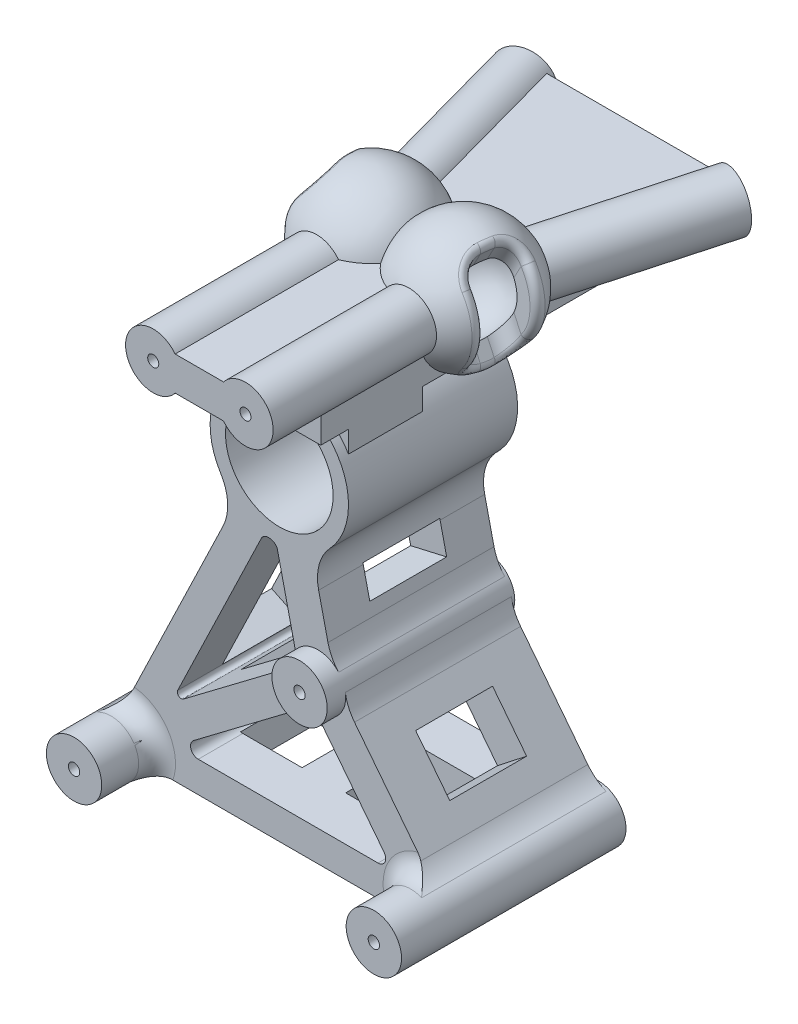
SolidWorks part; units mm, degrees
ref_plane "前视基准面" through (0, 0, 0) normal (0, 0, 1) x (1, 0, 0)
ref_plane "上视基准面" through (0, 0, 0) normal (0, 1, 0) x (1, 0, 0)
ref_plane "右视基准面" through (0, 0, 0) normal (1, 0, 0) x (0, 0, -1)
sketch "平面布局" plane through (0, 0, 0) normal (0, 1, 0) x (1, 0, 0)
  line L0 (-3, 0) -> (0, 0) construction
  line L1 (0, 0) -> (3, 0) construction
  line L2 (-3, -14.2) -> (-3, 0)
  line L3 (-3, 0) -> (-6.7739, 13.6893)
  line L4 (3, -14.2) -> (3, 0)
  line L5 (3, 0) -> (6.7739, 13.6893)
  line L6 (0, 0) -> (0, 13.6893) construction
  line L7 (0, 13.6893) -> (6.7739, 13.6893) construction
  line L8 (-6.7739, 13.6893) -> (0, 13.6893) construction
  line L9 (6.7739, 13.6893) -> (12.433, -1.2764) construction
  line L10 (12.433, -1.2764) -> (3, -14.2) construction
  line L11 (-6.7739, 13.6893) -> (-12.433, -1.2764) construction
  line L12 (-12.433, -1.2764) -> (-3, -14.2) construction
  line L13 (-12.433, -1.2764) -> (-3, 0) construction
  line L14 (3, 0) -> (12.433, -1.2764) construction
  dimension "D1" = 6
  dimension "D2" = 15.413
  dimension "D3" = 14.2
  dimension "D4" = 16
sketch "减速器布局" plane through (0, 0, 0) normal (0, 0, 1) x (1, 0, 0)
  line L0 (0, 0) -> (0, -27.1742) construction
  line L1 (0, -27.1742) -> (9.75, -27.1742) construction
  line L2 (0, -27.1742) -> (-9.75, -27.1742) construction
  line L3 (-3, 0) -> (0, 0) construction
  line L4 (-12.433, 0) -> (-3, 0) construction
  line L5 (0, 0) -> (3, 0) construction
  line L6 (12.433, 0) -> (3, 0) construction
  line L7 (3, 0) -> (12.433, 0) construction
  line L8 (9.75, -27.1742) -> (3, 0) construction
  line L9 (-3, 0) -> (-9.75, -27.1742) construction
  line L10 (9.75, -27.1742) -> (2.516, -17.9151) construction
  line L11 (-22.186, -2) -> (32.0919, -2) construction
  line L12 (0, 0) -> (0, -28.8801) construction
  line L13 (9.75, -27.1742) -> (16.95, -27.1742) construction
  line L14 (2.516, -17.9151) -> (0, -6.95) construction
  line L15 (0, -6.95) -> (0, 0) construction
  circle A0 centre (9.75, -27.1742) radius 11.75 construction
  circle A1 centre (-9.75, -27.1742) radius 11.75 construction
  circle A2 centre (2.516, -17.9151) radius 9.75 construction
  circle A3 centre (2.516, -17.9151) radius 2.5 construction
  circle A4 centre (-9.75, -27.1742) radius 1.8
  circle A5 centre (9.75, -27.1742) radius 1.8
  circle A6 centre (9.75, -27.1742) radius 10.25 construction
  circle A7 centre (-9.75, -27.1742) radius 10.25 construction
  circle A8 centre (2.516, -17.9151) radius 11.25 construction
  circle A9 centre (0, -28.8801) radius 3.5
  circle A10 centre (9.75, -27.1742) radius 9.125 construction
  circle A11 centre (-9.75, -27.1742) radius 9.125 construction
  circle A12 centre (9.75, -27.1742) radius 7.2 construction
  circle A13 centre (-9.75, -27.1742) radius 7.2 construction
  circle A14 centre (16.95, -27.1742) radius 1.6
  circle A15 centre (0, -6.95) radius 4.8
  dimension "D4" = 23.5
  dimension "D5" = 5
  dimension "D6" = 3.6
  dimension "D7" = 20.5
  dimension "D8" = 19.5
  dimension "D10" = 22.5
  dimension "D11" = 7
  dimension "D13" = 18.25
  dimension "D14" = 14.4
  dimension "D15" = 3.2
  dimension "D16" = 9.6
  dimension "D1" = 6
  dimension "D2" = 28
  dimension "D3" = 9.75
  dimension "D9" = 52
  dimension "D12" = 2
ref_plane "基准面1" through (3, 0, 14.2) normal (0, 0, -1) x (-1, 0, 0)
sketch "草图2" plane through (3, 0, 14.2) normal (0, 0, -1) x (-1, 0, 0)
  line L1 (4.5752, -1.1) -> (1.4248, -1.1)
  line L3 (4.5752, 1.1) -> (1.4248, 1.1)
  line L5 (4.5752, -1.1) -> (1.4248, 1.1) construction
  line L6 (4.5752, 1.1) -> (1.4248, -1.1) construction
  arc A0 (1.4248, 1.1) -> (1.4248, -1.1) centre (0, 0) ccw
  arc A1 (4.5752, -1.1) -> (4.5752, 1.1) centre (6, 0) ccw
  point P2 (3, 0)
  dimension "D1" = 3.6
  dimension "D2" = 2.2
extrude "凸台-拉伸1" add sketch "草图2" along normal up to vertex (14.2 mm away) up to point (-3, 0, 0)
ref_plane "基准面2" through (-6.7739, 0, -13.6893) normal (-0.2658, 0, -0.964) x (-0.964, 0, 0.2658)
sketch "草图3" plane through (-6.7739, 0, -13.6893) normal (-0.2658, 0, -0.964) x (-0.964, 0, 0.2658)
  line L0 (0, 0) -> (-2.8921, 0) construction
  line L1 (0, 0) -> (-6.5303, 0) construction
  circle A0 centre (0, 0) radius 1.8
  dimension "D1" = 3.6
extrude "凸台-拉伸2" add sketch "草图3" against normal blind 14
ref_plane "基准面3" through (6.7739, 0, -13.6893) normal (0.2658, 0, -0.964) x (-0.964, 0, -0.2658)
sketch "草图4" plane through (6.7739, 0, -13.6893) normal (0.2658, 0, -0.964) x (-0.964, 0, -0.2658)
  circle A0 centre (0, 0) radius 1.8
  dimension "D1" = 3.6
extrude "凸台-拉伸3" add sketch "草图4" against normal blind 14
sketch "草图10" plane through (0, 0, 0) normal (0, 1, 0) x (1, 0, 0)
  line L0 (-3, 0) -> (-6.7739, 13.6893) construction
  line L1 (-3, 0) -> (0, 0) construction
  line L2 (0, 0) -> (3, 0) construction
  line L3 (3, 0) -> (6.7739, 13.6893) construction
  line L4 (0, 13.6893) -> (6.7739, 13.6893) construction
  line L5 (-6.7739, 13.6893) -> (0, 13.6893) construction
  line L6 (-3, 0) -> (-6.7739, 13.6893)
  line L7 (-3, 0) -> (0, 0)
  line L8 (0, 0) -> (3, 0)
  line L9 (3, 0) -> (6.7739, 13.6893)
  line L10 (0, 13.6893) -> (6.7739, 13.6893)
  line L11 (-6.7739, 13.6893) -> (0, 13.6893)
extrude "凸台-拉伸4" add sketch "草图10" along normal mid plane 2.2
sketch "草图5" plane through (0, 0, 0) normal (0, 1, 0) x (1, 0, 0)
  line L0 (-7, 0) -> (-5.56, 0)
  line L1 (-0.44, 0) -> (0.44, 0)
  line L2 (5.56, 0) -> (7, 0)
  arc A0 (7, 0) -> (0, 2.6458) centre (3, 0) ccw
  arc A1 (0, 2.6458) -> (-7, 0) centre (-3, 0) ccw
  arc A2 (-5.56, 0) -> (-0.44, 0) centre (-3, 0) cw
  arc A3 (0.44, 0) -> (5.56, 0) centre (3, 0) cw
  dimension "D1" = 8
  dimension "D2" = 2.56
revolve "旋转1" add sketch "草图5" angle 360 about L0
sketch "草图8" plane through (0, 0, 0) normal (0, 1, 0) x (1, 0, 0)
  line L0 (-5.56, 0) -> (-0.44, 0)
  line L1 (0.44, 0) -> (5.56, 0)
  line L3 (-7, 0) -> (-5.56, 0)
  line L4 (-0.44, 0) -> (0.44, 0)
  line L5 (5.56, 0) -> (7, 0)
  line L7 (-0.44, 0) -> (0.44, 0)
  arc A4 (-0.44, 0) -> (-5.56, 0) centre (-3, 0) ccw
  arc A5 (5.56, 0) -> (0.44, 0) centre (3, 0) ccw
  arc A6 (7, 0) -> (0, 2.6458) centre (3, 0) ccw
  arc A7 (0, 2.6458) -> (-7, 0) centre (-3, 0) ccw
  arc A8 (-0.44, 0) -> (-5.56, 0) centre (-3, 0) ccw
  arc A9 (5.56, 0) -> (0.44, 0) centre (3, 0) ccw
  dimension "D1" = 0
revolve "切除-旋转2" cut sketch "草图8" angle 360 about L7 region at (-3, 0, -1.0865) region at (3, 0, -1.0865)
sketch "草图6" plane through (0, 0, 0) normal (0, 1, 0) x (1, 0, 0)
  line L0 (3, 0) -> (12.433, -1.2764) construction
  line L1 (3, 0) -> (12.433, -1.2764) construction
  line L2 (3, 0) -> (1.8263, -8.6738) construction
  line L3 (4.4608, -1.7113) -> (7.0032, -2.0554)
  line L4 (4.863, 1.2616) -> (7.4055, 0.9175)
  line L6 (3.2011, 1.4865) -> (12.6342, 0.21) construction
  line L7 (2.7989, -1.4865) -> (12.2319, -2.7629) construction
  arc A0 (4.4608, -1.7113) -> (4.863, 1.2616) centre (3, 0) ccw
  arc A1 (7.0032, -2.0554) -> (7.4055, 0.9175) centre (3, 0) ccw
  dimension "D1" = 4.5
  dimension "D2" = 9
  dimension "D3" = 1.5
  dimension "D4" = 1.5
revolve "切除-旋转1" cut sketch "草图6" angle 120 mid plane about L2
mirror "镜向1" about plane through (0, 0, 0) normal (1, 0, 0) of "切除-旋转1"
fillet "圆角1" radius 1.1 8 edges at (-4.6337, -2.5039, -1.2926) (-4.2315, -2.5039, 1.6803) (-4.2315, 2.5039, 1.6803) (-4.6337, 2.5039, -1.2926) (4.2315, -2.5039, 1.6803) (4.6337, -2.5039, -1.2926) (4.6337, 2.5039, -1.2926) (4.2315, 2.5039, 1.6803)
fillet "圆角2" radius 0.4 16 edges at (-6.8758, 0, -0.9892) (-5.2491, -3.2142, -0.7816) (-4.9819, -3.4641, 0.2682) (-5.0396, -3.0857, 1.5226) (-6.4735, 0, 1.9837) (-4.9605, 3.2142, 1.3512) (-4.9819, 3.4641, 0.2682) (-5.3709, 3.0857, -0.9258) (5.3709, -3.0857, -0.9258) (4.9819, -3.4641, 0.2682) (4.9605, -3.2142, 1.3512) (6.4735, 0, 1.9837) (5.0396, 3.0857, 1.5226) (4.9819, 3.4641, 0.2682) (5.2491, 3.2142, -0.7816) (6.8758, 0, -0.9892)
ref_plane "基准面4" through (0, -3.3, 0) normal (0, -1, 0) x (-1, 0, 0)
sketch "草图26" plane through (0, -3.3, 0) normal (0, -1, 0) x (-1, 0, 0)
  line L0 (0, 0) -> (0, -0.2) construction
  line L1 (-3.9, -10.2) -> (3.9, -10.2)
  line L2 (-3.9, -10.2) -> (-3.9, 9.8)
  line L3 (-3.9, 9.8) -> (3.9, 9.8)
  line L4 (3.9, -10.2) -> (3.9, 9.8)
  line L5 (-3.9, -10.2) -> (3.9, 9.8) construction
  line L6 (-3.9, 9.8) -> (3.9, -10.2) construction
  point P0 (0, -0.2)
  dimension "D1" = 7.8
  dimension "D2" = 20
  dimension "D3" = 0.2
extrude "凸台-拉伸9" add sketch "草图26" against normal up to body
sketch "草图12" plane through (0, 0, 0) normal (0, 0, 1) x (1, 0, 0)
  circle A0 centre (9.75, -27.1742) radius 1.8 construction
  circle A1 centre (9.75, -27.1742) radius 1.8
  circle A2 centre (-9.75, -27.1742) radius 1.8 construction
  circle A3 centre (-9.75, -27.1742) radius 1.8
  circle A4 centre (0, -6.95) radius 4.5
  circle A5 centre (2.516, -17.9151) radius 1.8
  circle A7 centre (0, -6.95) radius 3.5
  dimension "D1" = 7
  dimension "D2" = 9
extrude "凸台-拉伸5" add sketch "草图12" along normal blind 12.6 and the other way blind 2 separate body
sketch "草图13" plane through (0, 0, 12.6) normal (0, 0, 1) x (1, 0, 0)
  circle A1 centre (2.516, -17.9151) radius 1.8
  circle A2 centre (2.516, -17.9151) radius 1.8
  dimension "D1" = 0
extrude "切除-拉伸1" cut sketch "草图13" against normal blind 2.4
sketch "草图14" plane through (0, 0, 12.6) normal (0, 0, 1) x (1, 0, 0)
  circle A1 centre (0, -6.95) radius 4.5
  circle A2 centre (0, -6.95) radius 4.5
  dimension "D1" = 0
extrude "切除-拉伸2" cut sketch "草图14" against normal blind 3.6
sketch "草图15" plane through (0, 0, 0) normal (0, 0, 1) x (1, 0, 0)
  circle A0 centre (2.516, -17.9151) radius 0.37
  circle A1 centre (9.75, -27.1742) radius 0.37
  circle A2 centre (-9.75, -27.1742) radius 0.37
  dimension "D1" = 0.74
extrude "切除-拉伸3" cut sketch "草图15" against normal through all both and the other way through all
sketch "草图16" plane through (0, 0, 0) normal (0, 0, 1) x (1, 0, 0)
  line L0 (-9.75, -27.1742) -> (9.75, -27.1742) construction
  line L1 (9.75, -27.1742) -> (2.516, -17.9151) construction
  line L2 (2.516, -17.9151) -> (0, -6.95) construction
  line L3 (0, -6.95) -> (-9.75, -27.1742) construction
  line L4 (0, -6.95) -> (9.75, -27.1742) construction
  line L5 (-9.75, -27.1742) -> (2.516, -17.9151) construction
  line L6 (-2.8061, -10.4679) -> (-10.0008, -25.3918)
  line L7 (1.0463, -16.8758) -> (-0.1997, -11.4456)
  line L9 (-7.953, -27.0706) -> (1.9239, -19.6149)
  line L10 (-8.2533, -28.1742) -> (8.2533, -28.1742)
  line L11 (9.8696, -25.3782) -> (4.2876, -18.2335)
  line L12 (-9.75, -28.1742) -> (9.75, -28.1742) construction
  line L13 (-1.0045, -11.3365) -> (-8.1993, -26.2603)
  line L14 (-9.1579, -25.4744) -> (0.719, -18.0187)
  line L17 (-8.2533, -26.1742) -> (8.2533, -26.1742)
  line L21 (-0.9008, -6.5158) -> (-10.6508, -26.7399) construction
  line L22 (0.9008, -7.3843) -> (-8.8492, -27.6085) construction
  line L23 (10.6956, -26.4354) -> (3.4616, -17.1763) construction
  line L25 (7.9784, -26.8558) -> (2.3964, -19.7111)
  line L26 (-10.3525, -26.3761) -> (1.9135, -17.1169) construction
  line L27 (-9.75, -26.1742) -> (9.75, -26.1742) construction
  line L28 (-9.1475, -27.9723) -> (3.1185, -18.7132) construction
  line L30 (3.3855, -16.3391) -> (2.1396, -10.9089)
  circle A1 centre (0, -6.95) radius 4.5 construction
  circle A2 centre (2.516, -17.9151) radius 1.8 construction
  circle A3 centre (9.75, -27.1742) radius 1.8 construction
  circle A4 centre (-9.75, -27.1742) radius 1.8 construction
  circle A5 centre (0, -6.95) radius 4.5
  circle A6 centre (2.516, -17.9151) radius 1.8
  circle A7 centre (9.75, -27.1742) radius 1.8
  circle A8 centre (-9.75, -27.1742) radius 1.8
  point P3 (3.4906, -17.6914)
  point P5 (0.9747, -6.7264)
  point P12 (-0.9008, -7.3843)
  point P13 (8.8492, -27.6085)
  point P20 (8.962, -27.7899)
  point P21 (1.728, -18.5307)
  point P26 (1.5413, -18.1387)
  point P27 (-0.9747, -7.1737)
  point P28 (0.9008, -6.5158)
  point P29 (10.6508, -26.7399)
  dimension "D2" = 1.2
  dimension "D3" = 1.2
  dimension "D10" = 1.2
  dimension "D1" = 1
  dimension "D4" = 1
  dimension "D5" = 1
  dimension "D6" = 1.2
  dimension "D8" = 1
  dimension "D9" = 1
  dimension "D12" = 1
extrude "凸台-拉伸7" add sketch "草图16" along normal blind 9 and the other way blind 1.8 contours A6 L30 A5 L7 | A8 L14 L13 A5 L6 | A6 L14 L13 L17 L9 | A8 L10 A7 L25 L17 L9 | A7 L11 A6 L25 L17 | A7 L17 L25 | A8 L17 L13 L14 | A8 L9 L17 L13 region at (-5.3477, -17.9751, 0) region at (-8.1058, -25.1661, 0) region at (0.0882, -27.1948, 0) region at (1.5703, -13.7937, 0) region at (-3.1946, -22.2527, 0) region at (-7.6266, -26.4657, 0) region at (7.8774, -26.3936, 0) region at (6.1106, -22.4953, 0)
sketch "草图17" plane through (0, -1.1, 0) normal (0, -1, 0) x (1, 0, 0)
  line L0 (0, 0) -> (0, 6) construction
  line L2 (-3.9, 3.6) -> (3.9, 3.6)
  line L3 (-3.9, 3.6) -> (-3.9, 8.4)
  line L4 (-3.9, 8.4) -> (3.9, 8.4)
  line L5 (3.9, 3.6) -> (3.9, 8.4)
  line L6 (-3.9, 3.6) -> (3.9, 8.4) construction
  line L7 (-3.9, 8.4) -> (3.9, 3.6) construction
  dimension "D1" = 4.8
  dimension "D2" = 7.8
  dimension "D3" = 6
extrude "凸台-拉伸8" add sketch "草图17" along normal up to body
sketch "草图18" plane through (0, 0, 14.2) normal (0, 0, 1) x (1, 0, 0)
  line L0 (-12.433, 0) -> (-3, 0) construction
  line L1 (-12.433, 0) -> (-3, 0) construction
  line L2 (12.433, 0) -> (3, 0) construction
  line L3 (0, 0) -> (6.7739, 0) construction
  circle A0 centre (-3, 0) radius 0.36
  circle A1 centre (3, 0) radius 0.36
  arc A2 (3.9, -1.5588) -> (1.5752, 1.1) centre (3, 0) ccw construction
  arc A4 (-1.5752, 1.1) -> (-1.5752, -1.1) centre (-3, 0) ccw construction
  dimension "D1" = 0.72
extrude "切除-拉伸4" cut sketch "草图18" against normal blind 10
sketch "草图19" plane through (3.9858, 0, -14.458) normal (0.2658, 0, -0.964) x (-0.964, 0, -0.2658)
  circle A0 centre (-2.8921, 0) radius 0.36
  dimension "D1" = 0.72
extrude "切除-拉伸5" cut sketch "草图19" against normal blind 10
sketch "草图20" plane through (-3.9858, 0, -14.458) normal (-0.2658, 0, -0.964) x (-0.964, 0, 0.2658)
  circle A0 centre (2.8921, 0) radius 0.36
  dimension "D1" = 0.72
extrude "切除-拉伸6" cut sketch "草图20" against normal blind 10
sketch "草图21" plane through (-6.1835, -4.8311, 0) normal (0.788, 0.6157, 0) x (0, 0, -1)
  line L0 (-3.6, -17.0079) -> (-3.6, -21.5413) construction
  line L1 (-6.1, -23.3413) -> (-1.1, -23.3413)
  line L2 (-6.1, -23.3413) -> (-6.1, -19.7413)
  line L3 (-6.1, -19.7413) -> (-1.1, -19.7413)
  line L4 (-1.1, -23.3413) -> (-1.1, -19.7413)
  line L5 (-6.1, -23.3413) -> (-1.1, -19.7413) construction
  line L6 (-6.1, -19.7413) -> (-1.1, -23.3413) construction
  line L7 (-9, -17.0079) -> (1.8, -17.0079) construction
  line L8 (-3.6, -21.5413) -> (-9, -21.5413) construction
  line L9 (-9, -26.0746) -> (-9, -17.0079) construction
  point P0 (-3.6, -21.5413)
  dimension "D1" = 3.6
  dimension "D2" = 5
extrude "切除-拉伸7" cut sketch "草图21" against normal up to next
sketch "草图22" plane through (1.8179, -0.8764, 0) normal (-0.9008, 0.4343, 0) x (0, 0, 1)
  line L0 (3.6, -10.648) -> (3.6, -27.2155) construction
  line L1 (9, -10.648) -> (-1.8, -10.648) construction
  line L2 (9, -27.2155) -> (-1.8, -27.2155) construction
  line L3 (-1.8, -18.9318) -> (9, -18.9318) construction
  line L4 (-1.8, -10.648) -> (-1.8, -27.2155) construction
  line L5 (9, -10.648) -> (9, -27.2155) construction
  line L7 (1.1, -23.5318) -> (6.1, -23.5318)
  line L8 (1.1, -23.5318) -> (1.1, -14.3318)
  line L9 (1.1, -14.3318) -> (6.1, -14.3318)
  line L10 (6.1, -23.5318) -> (6.1, -14.3318)
  line L11 (1.1, -23.5318) -> (6.1, -14.3318) construction
  line L12 (1.1, -14.3318) -> (6.1, -23.5318) construction
  point P12 (3.6, -18.9318)
  dimension "D1" = 5
  dimension "D2" = 9.2
extrude "切除-拉伸8" cut sketch "草图22" against normal up to next
sketch "草图23" plane through (-0.3453, -0.0792, 0) normal (0.9747, 0.2236, 0) x (0, 0, -1)
  line L0 (-3.6, -11.111) -> (-3.6, -16.6824) construction
  line L1 (1.8, -11.111) -> (-9, -11.111) construction
  line L2 (1.8, -16.6824) -> (-9, -16.6824) construction
  line L3 (-9, -13.8967) -> (1.8, -13.8967) construction
  line L4 (-9, -16.6824) -> (-9, -11.111) construction
  line L5 (1.8, -16.6824) -> (1.8, -11.111) construction
  line L7 (-6.1, -14.8967) -> (-1.1, -14.8967)
  line L8 (-6.1, -14.8967) -> (-6.1, -12.8967)
  line L9 (-6.1, -12.8967) -> (-1.1, -12.8967)
  line L10 (-1.1, -14.8967) -> (-1.1, -12.8967)
  line L11 (-6.1, -14.8967) -> (-1.1, -12.8967) construction
  line L12 (-6.1, -12.8967) -> (-1.1, -14.8967) construction
  point P12 (-3.6, -13.8967)
  dimension "D1" = 5
  dimension "D2" = 2
extrude "切除-拉伸9" cut sketch "草图23" against normal up to next
sketch "草图24" plane through (8.9254, -11.8239, 0) normal (-0.6025, 0.7981, 0) x (0.7981, 0.6025, 0)
  line L0 (-15.1522, 1.8) -> (-15.1522, -9) construction
  line L1 (-20.0224, 1.8) -> (-10.2821, 1.8) construction
  line L2 (-20.0224, -9) -> (-10.2821, -9) construction
  line L4 (-17.9522, -6.1) -> (-12.3522, -6.1)
  line L5 (-17.9522, -6.1) -> (-17.9522, -1.1)
  line L6 (-17.9522, -1.1) -> (-12.3522, -1.1)
  line L7 (-12.3522, -6.1) -> (-12.3522, -1.1)
  line L8 (-17.9522, -6.1) -> (-12.3522, -1.1) construction
  line L9 (-17.9522, -1.1) -> (-12.3522, -6.1) construction
  point P6 (-15.1522, -3.6)
  dimension "D1" = 5
  dimension "D2" = 5.6
extrude "切除-拉伸10" cut sketch "草图24" against normal up to next
sketch "草图25" plane through (0, -28.1742, 0) normal (0, -1, 0) x (1, 0, 0)
  line L0 (0, 9) -> (0, -1.8) construction
  line L1 (-8.2533, 9) -> (8.2533, 9) construction
  line L2 (-8.2533, -1.8) -> (8.2533, -1.8) construction
  line L3 (-8.2533, 3.6) -> (-5.4178, 3.6) construction
  line L5 (-8.2533, 9) -> (-8.2533, -1.8) construction
  line L7 (-1.4178, 3.6) -> (1.4178, 3.6) construction
  line L8 (-5.4178, 1.1) -> (-1.4178, 1.1)
  line L9 (-5.4178, 1.1) -> (-5.4178, 6.1)
  line L10 (-5.4178, 6.1) -> (-1.4178, 6.1)
  line L11 (-1.4178, 1.1) -> (-1.4178, 6.1)
  line L12 (-5.4178, 1.1) -> (-1.4178, 6.1) construction
  line L13 (-5.4178, 6.1) -> (-1.4178, 1.1) construction
  line L14 (1.4178, 1.1) -> (5.4178, 1.1)
  line L15 (1.4178, 1.1) -> (1.4178, 6.1)
  line L16 (1.4178, 6.1) -> (5.4178, 6.1)
  line L17 (5.4178, 1.1) -> (5.4178, 6.1)
  line L18 (1.4178, 1.1) -> (5.4178, 6.1) construction
  line L19 (1.4178, 6.1) -> (5.4178, 1.1) construction
  line L20 (5.4178, 3.6) -> (8.2533, 3.6) construction
  line L21 (8.2533, 9) -> (8.2533, -1.8) construction
  point P10 (-3.4178, 3.6)
  point P18 (3.4178, 3.6)
  dimension "D1" = 4
  dimension "D2" = 5
extrude "切除-拉伸11" cut sketch "草图25" against normal up to next
fillet "圆角3" radius 0.5 8 edges at (0.719, -18.0187, 3.6) (1.0463, -16.8758, 3.6) (-6.7655, -26.1742, 3.6) (7.4459, -26.1742, 3.6) (2.3964, -19.7111, 3.6) (1.9239, -19.6149, 3.6) (-1.0045, -11.3365, 3.6) (-0.1997, -11.4456, 3.6)
fillet "圆角4" radius 0.25 1 edges at (-7.0551, -23.887, 3.6)
fillet "圆角5" radius 3 8 edges at (8.2533, -28.1742, 3.6) (-8.2533, -28.1742, 3.6) (-10.0008, -25.3918, 3.6) (-2.8061, -10.4679, 3.6) (3.3855, -16.3391, 3.6) (4.2876, -18.2335, 3.6) (9.8696, -25.3782, 3.6) (2.1396, -10.9089, 3.6)
fillet "圆角6" radius 1.2 2 edges at (-7.9959, -27.5781, 9) (8.1652, -26.3208, 9)
